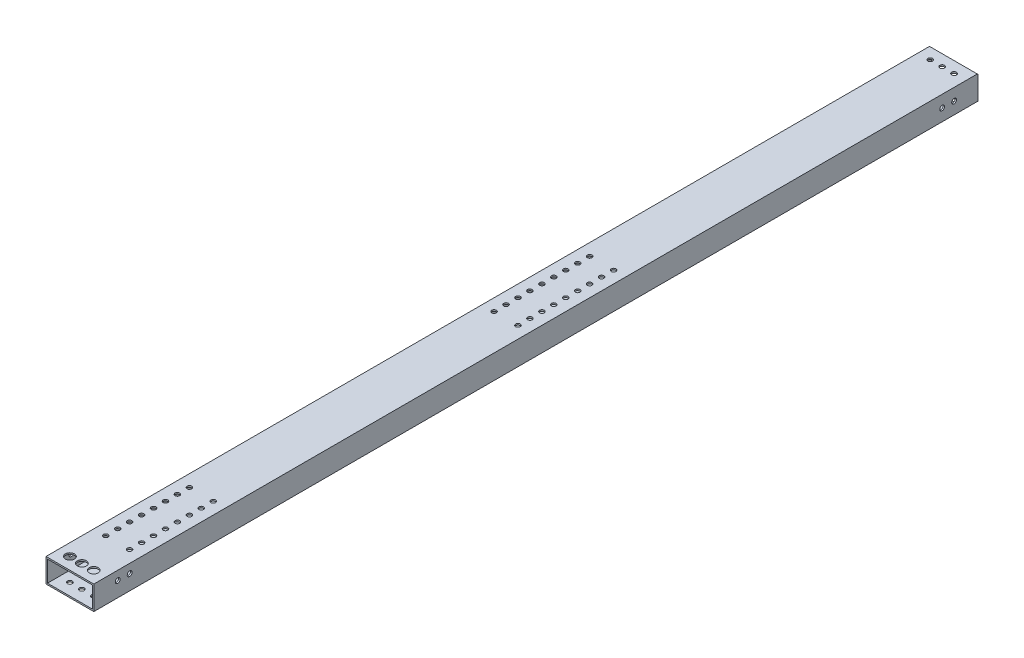
SolidWorks part; units mm, degrees
material "6061-T6 (SS)"
ref_plane "Front Plane" through (0, 0, 0) normal (0, 0, 1) x (1, 0, 0)
ref_plane "Top Plane" through (0, 0, 0) normal (0, 1, 0) x (1, 0, 0)
ref_plane "Right Plane" through (0, 0, 0) normal (1, 0, 0) x (0, 0, -1)
sketch "Sketch1" plane through (0, 0, 0) normal (0, 0, 1) x (1, 0, 0)
  line L0 (-23.8125, 11.1125) -> (23.8125, 11.1125)
  line L1 (-25.4, -12.7) -> (25.4, -12.7)
  line L2 (-25.4, -12.7) -> (-25.4, 12.7)
  line L3 (-25.4, 12.7) -> (25.4, 12.7)
  line L4 (25.4, -12.7) -> (25.4, 12.7)
  line L5 (-25.4, -12.7) -> (25.4, 12.7) construction
  line L6 (-25.4, 12.7) -> (25.4, -12.7) construction
  line L7 (23.8125, -11.1125) -> (23.8125, 11.1125)
  line L8 (-23.8125, -11.1125) -> (23.8125, -11.1125)
  line L9 (-23.8125, -11.1125) -> (-23.8125, 11.1125)
  point P0 (0, 0)
  dimension "D1" = 50.8
  dimension "D2" = 25.4
  dimension "D3" = 1.5875
extrude "Boss-Extrude1" add sketch "Sketch1" along normal mid plane 939.8
sketch "Sketch4" plane through (0, 12.7, 0) normal (0, 1, 0) x (1, 0, 0)
  line L0 (25.4, -469.9) -> (-25.4, -469.9) construction
  circle A0 centre (-12.7, -457.2) radius 4.826
  circle A1 centre (0, -457.2) radius 4.826
  circle A2 centre (12.7, -457.2) radius 4.826
  dimension "D1" = 9.652
  dimension "D2" = 12.7
  dimension "D3" = 12.7
  dimension "D4" = 12.7
extrude "Cut-Extrude3" cut sketch "Sketch4" against normal up to surface (1.5875 mm away) contours A0 | A1 | A2 region at (-12.7, 12.7, 457.2) region at (0, 12.7, 457.2) region at (12.7, 12.7, 457.2) up to face at (0, 11.1125, 0)
sketch "Sketch5" plane through (0, -12.7, 0) normal (0, -1, 0) x (1, 0, 0)
  circle A0 centre (-12.7, 457.2) radius 4.826 construction
  circle A1 centre (0, 457.2) radius 4.826 construction
  circle A2 centre (12.7, 457.2) radius 4.826 construction
  circle A3 centre (-12.7, 457.2) radius 4.826
  circle A4 centre (0, 457.2) radius 4.826
  circle A5 centre (12.7, 457.2) radius 4.826
  circle A6 centre (-12.7, 457.2) radius 2.5527
  circle A7 centre (0, 457.2) radius 2.5527
  circle A8 centre (12.7, 457.2) radius 2.5527
  dimension "D1" = 5.1054
extrude "Cut-Extrude4" cut sketch "Sketch5" against normal up to surface (1.5875 mm away) contours A8 | A7 | A6 region at (-12.7, -12.7, 457.2) region at (0, -12.7, 457.2) region at (12.7, -12.7, 457.2) up to face at (0, -11.1125, 0)
sketch "Sketch6" plane through (0, -12.7, 0) normal (0, -1, 0) x (1, 0, 0)
  line L0 (-25.4, -469.9) -> (25.4, -469.9) construction
  circle A0 centre (-12.7, -457.2) radius 2.5527
  circle A1 centre (0, -457.2) radius 2.5527
  circle A2 centre (12.7, -457.2) radius 2.5527
  dimension "D1" = 5.1054
  dimension "D2" = 12.7
  dimension "D3" = 12.7
  dimension "D4" = 12.7
extrude "Cut-Extrude5" cut sketch "Sketch6" against normal through all contours A2 | A1 | A0 region at (-12.7, -12.7, -457.2) region at (0, -12.7, -457.2) region at (12.7, -12.7, -457.2)
sketch "Sketch7" plane through (25.4, 0, 0) normal (1, 0, 0) x (0, 0, -1)
  line L0 (-469.9, -12.7) -> (-469.9, 12.7) construction
  line L2 (469.9, -12.7) -> (469.9, 12.7) construction
  line L3 (-469.9, -12.7) -> (469.9, -12.7) construction
  circle A0 centre (-457.2, 3.175) radius 2.5527
  circle A1 centre (-444.5, 3.175) radius 2.5527
  circle A2 centre (-431.8, 3.175) radius 2.5527
  circle A3 centre (-419.1, 3.175) radius 2.5527
  circle A4 centre (457.2, 0) radius 2.5527
  circle A5 centre (444.5, 0) radius 2.5527
  circle A6 centre (431.8, 0) radius 2.5527
  dimension "D1" = 5.1054
  dimension "D7" = 5.1054
  dimension "D8" = 12.7
  dimension "D2" = 12.7
  dimension "D3" = 12.7
  dimension "D4" = 12.7
  dimension "D5" = 12.7
  dimension "D6" = 15.875
  dimension "D9" = 12.7
  dimension "D10" = 12.7
  dimension "D11" = 12.7
extrude "Cut-Extrude6" cut sketch "Sketch7" against normal through all contours A6 | A5 | A1 | A2 region at (25.4, 3.175, 444.5) region at (25.4, 3.175, 431.8) region at (25.4, 0, -444.5) region at (25.4, 0, -431.8)
sketch "Sketch10" plane through (0, 12.7, 0) normal (0, 1, 0) x (1, 0, 0)
  line L1 (25.4, -469.9) -> (-25.4, -469.9) construction
  line L3 (-25.4, -469.9) -> (-25.4, 469.9) construction
  circle A0 centre (-12.7, -419.1) radius 2.4892
  circle A5 centre (12.7, -419.1) radius 2.4892
  circle A6 centre (-12.7, -406.4) radius 2.4892
  circle A7 centre (12.7, -406.4) radius 2.4892
  circle A8 centre (-12.7, -393.7) radius 2.4892
  circle A9 centre (12.7, -393.7) radius 2.4892
  circle A10 centre (-12.7, -381) radius 2.4892
  circle A11 centre (12.7, -381) radius 2.4892
  circle A12 centre (-12.7, -368.3) radius 2.4892
  circle A13 centre (12.7, -368.3) radius 2.4892
  circle A14 centre (-12.7, -355.6) radius 2.4892
  circle A15 centre (12.7, -355.6) radius 2.4892
  circle A16 centre (-12.7, -342.9) radius 2.4892
  circle A17 centre (12.7, -342.9) radius 2.4892
  circle A18 centre (-12.7, -330.2) radius 2.4892
  circle A19 centre (12.7, -330.2) radius 2.4892
  circle A20 centre (-12.7, -6.35) radius 2.4892
  circle A21 centre (12.7, -6.35) radius 2.4892
  circle A22 centre (-12.7, 6.35) radius 2.4892
  circle A23 centre (12.7, 6.35) radius 2.4892
  circle A24 centre (-12.7, 19.05) radius 2.4892
  circle A25 centre (12.7, 19.05) radius 2.4892
  circle A26 centre (-12.7, 31.75) radius 2.4892
  circle A27 centre (12.7, 31.75) radius 2.4892
  circle A28 centre (-12.7, 44.45) radius 2.4892
  circle A29 centre (12.7, 44.45) radius 2.4892
  circle A30 centre (-12.7, 57.15) radius 2.4892
  circle A31 centre (12.7, 57.15) radius 2.4892
  circle A32 centre (-12.7, 69.85) radius 2.4892
  circle A33 centre (12.7, 69.85) radius 2.4892
  circle A34 centre (-12.7, 82.55) radius 2.4892
  circle A35 centre (12.7, 82.55) radius 2.4892
  circle A36 centre (-12.7, 95.25) radius 2.4892
  circle A37 centre (12.7, 95.25) radius 2.4892
  dimension "D1" = 25.4
  dimension "D3" = 4.9784
  dimension "D2" = 12.7
  dimension "D4" = 50.8
  dimension "D5" = 12.7
  dimension "D6" = 323.85
  dimension "D8" = 12.7
  dimension "D9" = 9
extrude "Cut-Extrude8" cut sketch "Sketch10" against normal up to next (1.5875 mm away)
chamfer "Chamfer1" distance 0.762 angle 45 1 edges at (0, 12.7, -469.9)
